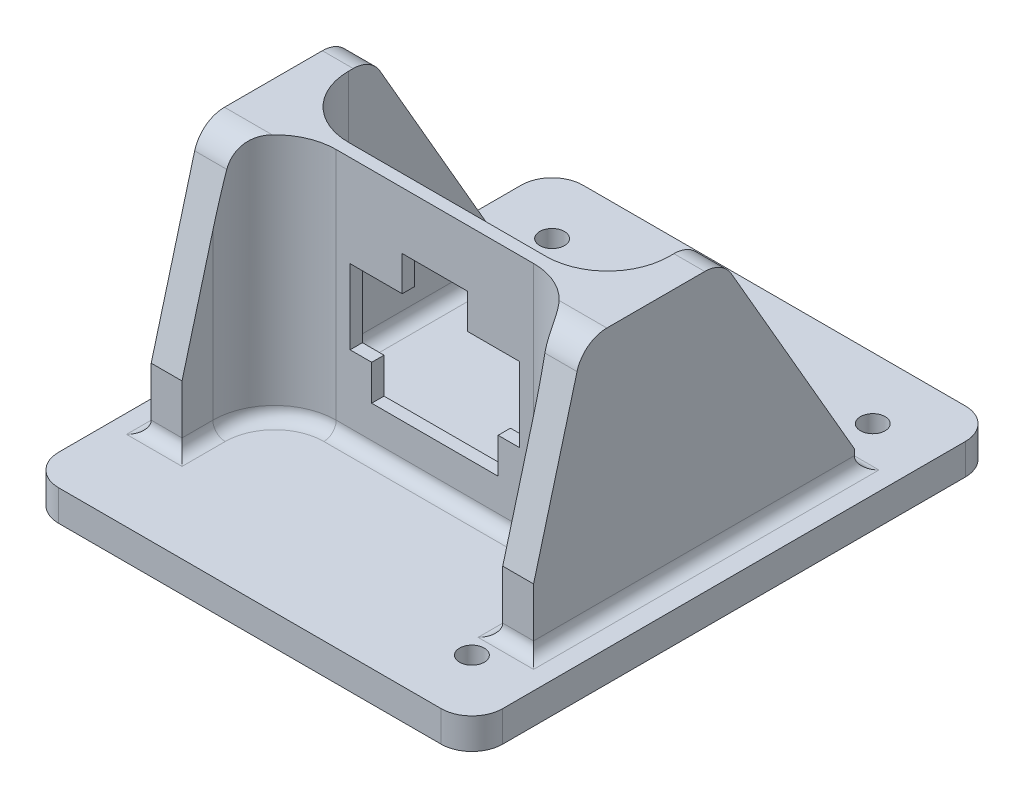
SolidWorks part; units mm, degrees
ref_plane "Front Plane" through (0, 0, 0) normal (0, 0, 1) x (1, 0, 0)
ref_plane "Top Plane" through (0, 0, 0) normal (0, 1, 0) x (1, 0, 0)
ref_plane "Right Plane" through (0, 0, 0) normal (1, 0, 0) x (0, 0, -1)
sketch "Sketch1" plane through (0, 0, 0) normal (0, 1, 0) x (1, 0, 0)
  line L0 (52, 0) -> (52, -10) construction
  line L1 (0, 0) -> (52, 0)
  line L2 (0, 0) -> (0, 65)
  line L3 (0, 65) -> (52, 65)
  line L4 (52, 0) -> (52, 65)
  line L5 (52, -10) -> (62, -10) construction
  line L7 (62, -10) -> (-10, -10)
  line L8 (62, -10) -> (62, 75)
  line L9 (62, 75) -> (-10, 75)
  line L10 (-10, -10) -> (-10, 75)
  circle A0 centre (0, 65) radius 2
  circle A1 centre (52, 65) radius 2
  circle A2 centre (52, 0) radius 2
  dimension "D1" = 52
  dimension "D2" = 65
  dimension "D3" = 10
  dimension "D4" = 10
  dimension "D5" = 85
  dimension "D6" = 72
extrude "Boss-Extrude1" add sketch "Sketch1" along normal blind 5 contours L10 L7 L8 L9 L2 A0 L3 A1 L4 A2 L1 | L1 A2 L4 A1 L3 A0 L2 region at (25.9766, 0, -32.4705) region at (26, 0, 8.886)
sketch "Sketch2" plane through (0, 5, 0) normal (0, 1, 0) x (1, 0, 0)
  line L0 (-10, -10) -> (-5, -10) construction
  line L1 (62, -10) -> (-10, -10) construction
  line L2 (-5, -10) -> (-5, 20) construction
  line L3 (26, 22) -> (26, 75) construction
  line L4 (-5, 20) -> (57, 20)
  line L5 (-5, 20) -> (-5, 22)
  line L6 (-5, 22) -> (57, 22)
  line L7 (57, 20) -> (57, 22)
  line L8 (-5, 22) -> (0, 22)
  line L9 (-5, 22) -> (-5, 57)
  line L10 (-5, 57) -> (0, 57)
  line L11 (0, 22) -> (0, 57)
  line L12 (-5, 20) -> (0, 20)
  line L13 (-5, 20) -> (-5, 5)
  line L14 (-5, 5) -> (0, 5)
  line L15 (0, 20) -> (0, 5)
  line L18 (57, 5) -> (52, 5)
  line L19 (52, 20) -> (52, 5)
  line L20 (57, 20) -> (52, 20)
  line L21 (57, 20) -> (57, 5)
  line L22 (57, 57) -> (52, 57)
  line L23 (52, 22) -> (52, 57)
  line L24 (57, 22) -> (52, 22)
  line L25 (57, 22) -> (57, 57)
  dimension "D1" = 30
  dimension "D2" = 5
  dimension "D3" = 2
  dimension "D4" = 62
  dimension "D5" = 35
  dimension "D6" = 5
  dimension "D7" = 15
  dimension "D8" = 5
extrude "Boss-Extrude2" add sketch "Sketch2" along normal blind 40 contours L15 L4 L13 L14 | L4 L7 L6 L5 | L21 L4 L19 L18 | L6 L25 L22 L23 | L6 L11 L10 L9 region at (26, 5, -21) region at (-2.5, 5, -12.5) region at (-2.5, 5, -39.5) region at (54.5, 5, -12.5) region at (54.5, 5, -39.5)
sketch "Sketch3" plane through (0, 0, -20) normal (0, 0, 1) x (1, 0, 0)
  line L1 (26, 35) -> (30.55, 35)
  line L17 (26, 45) -> (26, 35) construction
  line L18 (0, 45) -> (52, 45) construction
  line L19 (30.55, 35) -> (30.55, 29.35)
  line L20 (30.55, 29.35) -> (39, 29.35)
  line L21 (39, 29.35) -> (39, 18.75)
  line L22 (39, 18.75) -> (35.5, 18.75)
  line L23 (35.5, 18.75) -> (35.5, 13)
  line L24 (35.5, 13) -> (16.5, 13)
  line L25 (16.5, 13) -> (16.5, 18.75)
  line L26 (16.5, 18.75) -> (13, 18.75)
  line L27 (13, 18.75) -> (13, 29.35)
  line L28 (13, 29.35) -> (21.45, 29.35)
  line L29 (21.45, 29.35) -> (21.45, 35)
  line L30 (21.45, 35) -> (26, 35)
extrude "Cut-Extrude1" cut sketch "Sketch3" against normal blind 5
extrude "Cut-Extrude-Thin1" cut sketch "Sketch3<3>" against normal blind 5 thin thin type one direction wall 0.75
sketch "Sketch3<3>" plane through (0, 0, -20) normal (0, 0, 1) x (1, 0, 0) same geometry as "Sketch3"
fillet "Fillet1" radius 10 4 edges at (0, 25, -22) (52, 25, -22) (52, 25, -20) (0, 25, -20)
chamfer "Chamfer1" distance 37 angle 30 2 edges at (-2.5, 45, -57) (54.5, 45, -57) first distance on face at (-2.5, 25, -57) first distance on face at (54.5, 25, -57)
chamfer "Chamfer2" distance 30 angle 15 2 edges at (54.5, 45, -5) (-2.5, 45, -5) first distance on face at (54.5, 25, -5) first distance on face at (-2.5, 25, -5)
fillet "Fillet2" radius 2 16 edges at (54.5, 5, -57) (-2.5, 5, -57) (54.5, 5, -5) (-2.5, 5, -5) (0, 5, -44.5) (2.9289, 5, -24.9289) (26, 5, -22) (49.0711, 5, -24.9289) (52, 5, -7.5) (49.0711, 5, -17.0711) (26, 5, -20) (2.9289, 5, -17.0711) (52, 5, -44.5) (57, 5, -31) (0, 5, -7.5) (-5, 5, -31)
fillet "Fillet4" radius 5 8 edges at (-2.2636, 45, -13.0385) (54.2636, 45, -13.0385) (54.5, 45, -35.638) (-2.5, 45, -35.638) (62, 2.5, -75) (62, 2.5, 10) (-10, 2.5, -75) (-10, 2.5, 10)
